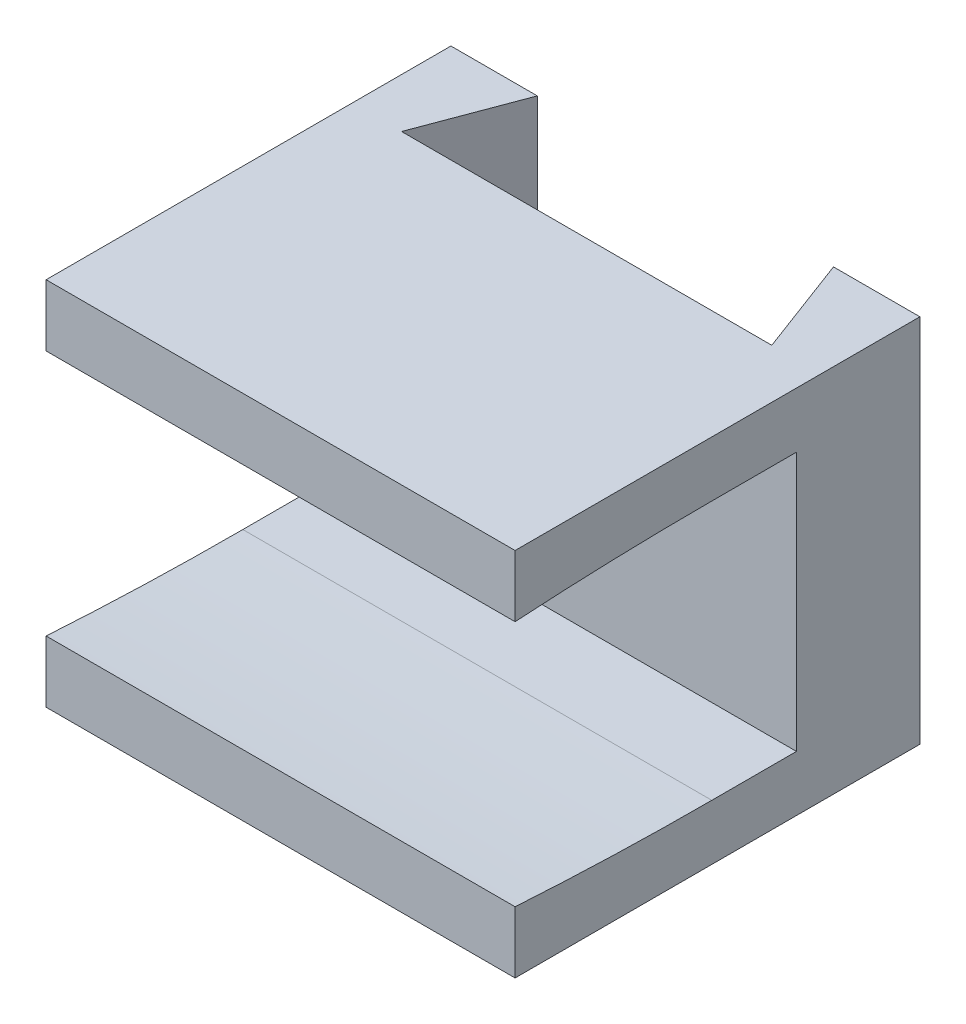
SolidWorks part; units mm, degrees
ref_plane "Front Plane" through (0, 0, 0) normal (0, 0, 1) x (1, 0, 0)
ref_plane "Top Plane" through (0, 0, 0) normal (0, 1, 0) x (1, 0, 0)
ref_plane "Right Plane" through (0, 0, 0) normal (1, 0, 0) x (0, 0, -1)
sketch "Sketch2" plane through (0, 0, 0) normal (0, 1, 0) x (1, 0, 0)
  line L0 (0, 0) -> (15, 0)
  line L1 (7.5, 0) -> (7.5, 16.6821) construction
  line L2 (15, 0) -> (13.5, 4)
  line L3 (13.5, 4) -> (15, 4)
  line L6 (1.5, 4) -> (0, 4)
  line L7 (0, 0) -> (1.5, 4)
  line L8 (15, 4) -> (17, 4)
  line L9 (17, 4) -> (17, -1)
  line L10 (17, -1) -> (-2, -1)
  line L11 (-2, -1) -> (-2, 4)
  line L12 (-2, 4) -> (0, 4)
  dimension "D1" = 15
  dimension "D2" = 1.5
  dimension "D3" = 4
  dimension "D4" = 2
  dimension "D5" = 2
  dimension "D6" = 1
  dimension "D7" = 19
extrude "Boss-Extrude1" add sketch "Sketch2" along normal blind 15
sketch "Sketch4" plane through (17, 0, 0) normal (1, 0, 0) x (0, 0, -1)
  line L0 (4, 7.5) -> (-4.3727, 7.5) construction
  line L1 (4, 15) -> (4, 0) construction
sketch "Sketch5" plane through (17, 0, 0) normal (1, 0, 0) x (0, 0, -1)
  line L1 (-1, 15) -> (-1, 0) construction
  line L2 (-1, 2.25) -> (-4.43, 2.25)
  line L3 (-1, 0) -> (-12.4, 0)
  line L4 (-12.4, 0) -> (-12.4, 2.5)
  line L5 (-1, 2.25) -> (-1, 0)
  line L6 (-1, 7.5) -> (-15.1852, 7.5) construction
  line L7 (-1, 12.75) -> (-4.43, 12.75)
  line L8 (-12.4, 15) -> (-12.4, 12.5)
  line L9 (-1, 15) -> (-12.4, 15)
  line L10 (-1, 12.75) -> (-1, 15)
  arc A1 (-4.43, 2.25) -> (-12.4, 2.5) centre (-4.43, 129.4168) cw
  arc A2 (-4.43, 12.75) -> (-12.4, 12.5) centre (-4.43, -114.4168) ccw
  dimension "D1" = 5.25
  dimension "D2" = 3.43
  dimension "D3" = 11.4
  dimension "D4" = 2.25
  dimension "D5" = 2.5
extrude "Boss-Extrude2" add sketch "Sketch5" against normal blind 19
